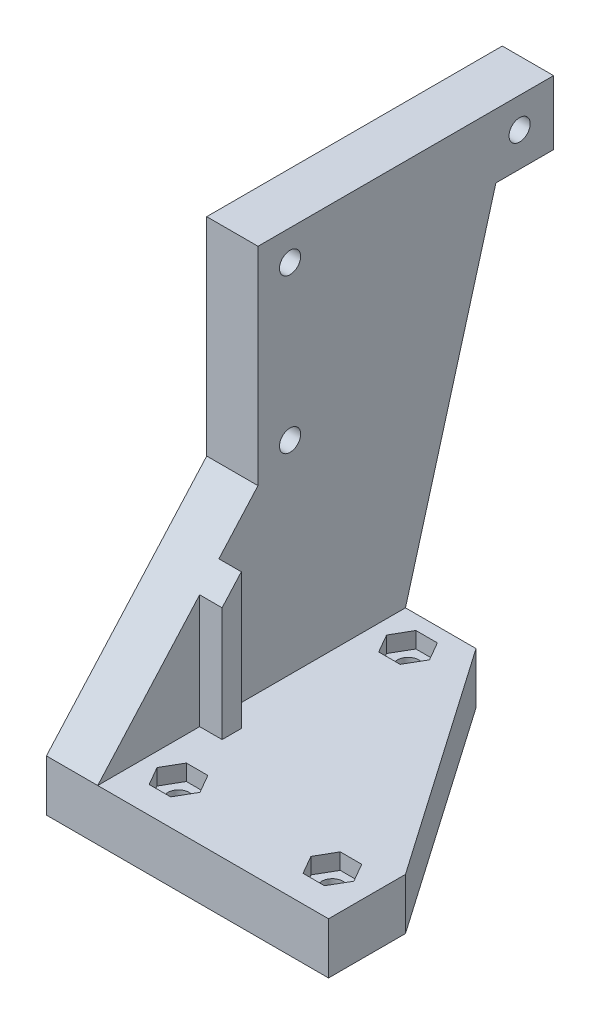
SolidWorks part; units mm, degrees
material "Copper"
ref_plane "Front Plane" through (0, 0, 0) normal (0, 0, 1) x (1, 0, 0)
ref_plane "Top Plane" through (0, 0, 0) normal (0, 1, 0) x (1, 0, 0)
ref_plane "Right Plane" through (0, 0, 0) normal (1, 0, 0) x (0, 0, -1)
sketch "Sketch1" plane through (0, 0, 0) normal (0, 1, 0) x (1, 0, 0)
  line L0 (-30.2016, 21.4588) -> (-19.2016, 21.4588)
  line L1 (5.7984, -26.5412) -> (5.7984, -14.5412)
  line L2 (-30.2016, 21.4588) -> (-30.2016, -26.5412)
  line L3 (-30.2016, -26.5412) -> (5.7984, -26.5412)
  line L4 (5.7984, -14.5412) -> (-19.2016, 21.4588)
  circle A0 centre (-24.6516, 16.3088) radius 1.65
  circle A1 centre (-24.6516, -19.4912) radius 1.65
  circle A2 centre (-0.6516, -19.4912) radius 1.65
  dimension "D3" = 3.3
  dimension "D6" = 3.3
  dimension "D9" = 3.3
  dimension "D1" = 48
  dimension "D2" = 5.15
  dimension "D4" = 5.55
  dimension "D5" = 11
  dimension "D7" = 35.8
  dimension "D8" = 5.55
  dimension "D10" = 24
  dimension "D11" = 35.8
  dimension "D12" = 12
extrude "Boss-Extrude1" add sketch "Sketch1" along normal blind 8
sketch "Sketch3" plane through (-30.2016, 0, 0) normal (-1, 0, 0) x (0, 0, 1)
  line L0 (-21.4588, 8) -> (26.5412, 8) construction
  line L1 (-44.5588, 58.3345) -> (-35.5588, 58.3345)
  line L2 (-35.5588, 58.3345) -> (-21.4588, 8)
  line L5 (26.5412, 8) -> (26.5412, 0) construction
  line L7 (-21.4588, 0) -> (26.5412, 0)
  line L8 (26.5412, 0) -> (26.5412, 8)
  line L9 (26.5412, 8) -> (1.5412, 36)
  line L10 (1.5412, 36) -> (1.5412, 68.3345)
  line L11 (1.5412, 68.3345) -> (-44.5588, 68.3345)
  line L12 (-44.5588, 68.3345) -> (-44.5588, 58.3345)
  line L14 (-21.4588, 8) -> (-21.4588, 0)
  circle A0 centre (-3.4588, 39.65) radius 1.65
  circle A1 centre (-3.4588, 63.65) radius 1.65
  circle A2 centre (-39.2588, 63.6645) radius 1.65
  dimension "D1" = 3.3
  dimension "D4" = 3.3
  dimension "D6" = 3.3
  dimension "D2" = 31.65
  dimension "D3" = 30
  dimension "D5" = 24
  dimension "D7" = 35.8
  dimension "D8" = 9
  dimension "D9" = 28
  dimension "D10" = 5
  dimension "D11" = 5.3
  dimension "D12" = 10
  dimension "D13" = 0
  dimension "D14" = 4.67
ref_axis "Axis1" through (-24.6516, 8, 19.4912) along (0, -1, 0)
extrude "Boss-Extrude2" add sketch "Sketch3" along normal blind 8
sketch "Sketch4" plane through (0, 8, 0) normal (0, 1, 0) x (1, 0, 0)
  line L1 (-26.3266, 13.4076) -> (-22.9766, 13.4076)
  line L2 (-22.9766, 13.4076) -> (-21.3016, 16.3088)
  line L3 (-21.3016, 16.3088) -> (-22.9766, 19.2099)
  line L4 (-22.9766, 19.2099) -> (-26.3266, 19.2099)
  line L5 (-26.3266, 19.2099) -> (-28.0016, 16.3088)
  line L6 (-28.0016, 16.3088) -> (-26.3266, 13.4076)
  line L7 (-22.9766, -16.5901) -> (-26.3266, -16.5901)
  line L8 (-26.3266, -16.5901) -> (-28.0016, -19.4912)
  line L9 (-28.0016, -19.4912) -> (-26.3266, -22.3924)
  line L10 (-26.3266, -22.3924) -> (-22.9766, -22.3924)
  line L11 (-22.9766, -22.3924) -> (-21.3016, -19.4912)
  line L12 (-21.3016, -19.4912) -> (-22.9766, -16.5901)
  line L13 (1.0234, -16.5901) -> (-2.3266, -16.5901)
  line L14 (-2.3266, -16.5901) -> (-4.0016, -19.4912)
  line L15 (-4.0016, -19.4912) -> (-2.3266, -22.3924)
  line L16 (-2.3266, -22.3924) -> (1.0234, -22.3924)
  line L17 (1.0234, -22.3924) -> (2.6984, -19.4912)
  line L18 (2.6984, -19.4912) -> (1.0234, -16.5901)
  circle A0 centre (-24.6516, 16.3088) radius 2.9012 construction
  circle A1 centre (-24.6516, -19.4912) radius 2.9012 construction
  circle A2 centre (-0.6516, -19.4912) radius 2.9012 construction
  dimension "D1" = 3.35
  dimension "D2" = 3.35
  dimension "D3" = 3.35
extrude "Cut-Extrude1" cut sketch "Sketch4" against normal blind 2.5
sketch "Sketch5" plane through (-30.2016, 0, 0) normal (1, 0, 0) x (0, 0, -1)
  line L0 (21.4588, 8) -> (-26.5412, 8) construction
  line L1 (-10.6412, 8) -> (-7.6412, 8)
  line L2 (-10.6412, 8) -> (-10.6412, 25.808)
  line L3 (-10.6412, 25.808) -> (-7.6412, 29.168)
  line L4 (-7.6412, 8) -> (-7.6412, 29.168)
  line L5 (-26.5412, 8) -> (-1.5412, 36) construction
  circle A0 centre (3.4588, 39.65) radius 1.65 construction
  dimension "D1" = 11.1
  dimension "D2" = 3
extrude "Boss-Extrude3" add sketch "Sketch5" along direction (1, 0, 0) on the side of the normal blind 3.5
